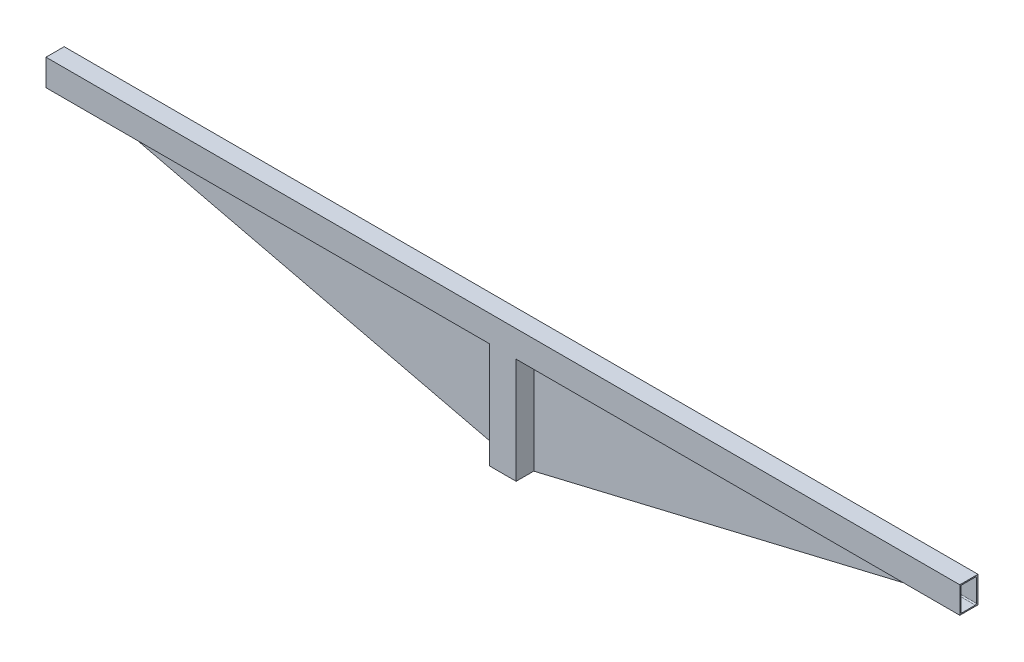
SolidWorks part; units mm, degrees
material "ASTM A500 Grade B Steel"
ref_plane "Front Plane" through (0, 0, 0) normal (0, 0, 1) x (1, 0, 0)
ref_plane "Top Plane" through (0, 0, 0) normal (0, 1, 0) x (1, 0, 0)
ref_plane "Right Plane" through (0, 0, 0) normal (1, 0, 0) x (0, 0, -1)
sketch "Sketch1" plane through (0, 0, 0) normal (1, 0, 0) x (0, 0, -1)
  line L0 (-95.25, 12.7) -> (-95.25, 139.7)
  line L1 (0, 0) -> (-101.6, 0)
  line L2 (0, 0) -> (0, 152.4)
  line L3 (0, 152.4) -> (-101.6, 152.4)
  line L4 (-101.6, 0) -> (-101.6, 152.4)
  line L5 (-12.7, 146.05) -> (-88.9, 146.05)
  line L6 (-6.35, 12.7) -> (-6.35, 139.7)
  line L7 (-12.7, 6.35) -> (-88.9, 6.35)
  line L8 (-95.25, 6.35) -> (-95.25, 146.05) construction
  line L9 (-6.35, 6.35) -> (-95.25, 6.35) construction
  line L10 (-6.35, 6.35) -> (-6.35, 146.05) construction
  line L11 (-6.35, 146.05) -> (-95.25, 146.05) construction
  arc A0 (-95.25, 12.7) -> (-88.9, 6.35) centre (-88.9, 12.7) ccw
  arc A1 (-6.35, 12.7) -> (-12.7, 6.35) centre (-12.7, 12.7) cw
  arc A2 (-12.7, 146.05) -> (-6.35, 139.7) centre (-12.7, 139.7) cw
  arc A3 (-95.25, 139.7) -> (-88.9, 146.05) centre (-88.9, 139.7) cw
  dimension "D4" = 6.35
  dimension "D2" = 101.6
  dimension "D3" = 6.35
extrude "Boss-Extrude1" add sketch "Sketch1" along normal blind 5265.2
sketch "Sketch2" plane through (0, 0, 0) normal (0, -1, 0) x (-1, 0, 0)
  line L0 (-5265.2, -101.6) -> (0, -101.6) construction
  line L1 (-2556.4, -101.6) -> (-2708.8, -101.6)
  line L2 (-2556.4, -101.6) -> (-2556.4, 0)
  line L3 (-2556.4, 0) -> (-2708.8, 0)
  line L4 (-2708.8, -101.6) -> (-2708.8, 0)
  line L5 (-5265.2, 0) -> (0, 0) construction
  line L6 (-2562.75, -88.9) -> (-2562.75, -12.7)
  line L7 (-2569.1, -6.35) -> (-2696.1, -6.35)
  line L8 (-2702.45, -88.9) -> (-2702.45, -12.7)
  line L9 (-2569.1, -95.25) -> (-2696.1, -95.25)
  line L10 (-2562.75, -95.25) -> (-2562.75, -6.35) construction
  line L11 (-2562.75, -6.35) -> (-2702.45, -6.35) construction
  line L12 (-2702.45, -95.25) -> (-2702.45, -6.35) construction
  line L13 (-2562.75, -95.25) -> (-2702.45, -95.25) construction
  arc A0 (-2562.75, -12.7) -> (-2569.1, -6.35) centre (-2569.1, -12.7) ccw
  arc A1 (-2702.45, -12.7) -> (-2696.1, -6.35) centre (-2696.1, -12.7) cw
  arc A2 (-2702.45, -88.9) -> (-2696.1, -95.25) centre (-2696.1, -88.9) ccw
  arc A3 (-2562.75, -88.9) -> (-2569.1, -95.25) centre (-2569.1, -88.9) cw
  point P24 (-2632.6, -101.6)
  point P25 (-2632.6, -101.6)
  dimension "D2" = 6.35
  dimension "D1" = 6.35
extrude "Boss-Extrude2" add sketch "Sketch2" along normal blind 609.6
sketch "Sketch3" plane through (0, 0, 0) normal (0, 0, -1) x (-1, 0, 0)
  line L0 (-2708.8, -609.6) -> (-2556.4, -609.6)
  line L1 (-2556.4, -609.6) -> (-2708.8, -609.6) construction
  line L2 (-2708.8, -609.6) -> (-2708.8, 0) construction
  line L3 (-2556.4, -609.6) -> (0, 0)
  line L4 (-2556.4, 0) -> (0, 0) construction
  line L5 (0, 0) -> (0, 152.4)
  line L6 (-5265.2, 152.4) -> (0, 152.4) construction
  line L7 (0, 152.4) -> (-5265.2, 152.4)
  line L8 (-5265.2, 152.4) -> (-5265.2, 0)
  line L9 (-5265.2, 0) -> (-2708.8, 0) construction
  line L10 (-5265.2, 0) -> (-2708.8, -609.6)
  line L11 (-5265.2, 0) -> (-5265.2, 152.4) construction
  line L12 (0, 0) -> (0, 152.4) construction
  point P16 (-2465.7713, -609.6)
  point P17 (-2708.8, -609.6)
  point P19 (-5210.8951, 0)
extrude "Boss-Extrude3" add sketch "Sketch3" along normal blind 3.175
equation "\"D4@Sketch1\"= \"D3@Sketch1\""
equation "\"D2@Sketch2\"=\"D1@Sketch2\""
